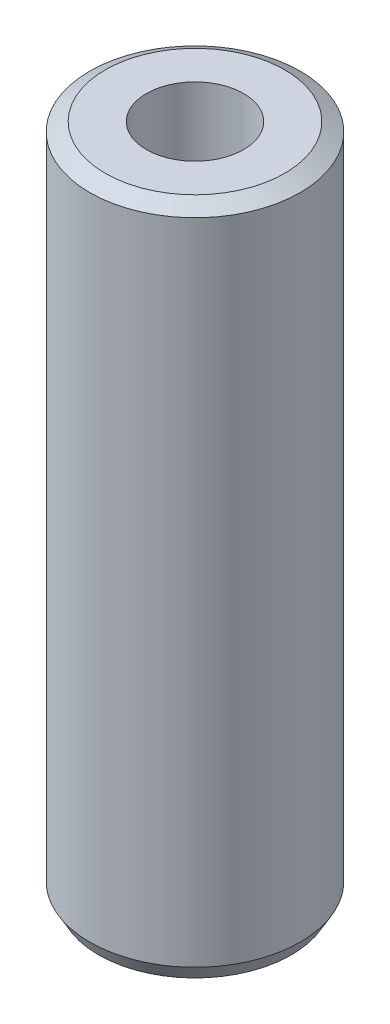
SolidWorks part; units mm, degrees
ref_plane "Front Plane" through (0, 0, 0) normal (0, 0, 1) x (1, 0, 0)
ref_plane "Top Plane" through (0, 0, 0) normal (0, 1, 0) x (1, 0, 0)
ref_plane "Right Plane" through (0, 0, 0) normal (1, 0, 0) x (0, 0, -1)
sketch "Sketch1" plane through (0, 0, 0) normal (0, 1, 0) x (1, 0, 0)
  circle A0 centre (0, 0) radius 55
  dimension "SHAFT_OD" = 110
extrude "Boss-Extrude1" add sketch "Sketch1" along normal blind 351.9378
sketch "Sketch2" plane through (0, 0, 0) normal (0, 1, 0) x (1, 0, 0)
  circle A0 centre (0, 0) radius 25.4016
  dimension "BORE_D" = 50.8031
extrude "Cut-Extrude1" cut sketch "Sketch2" along normal through all
chamfer "Chamfer1" distance 4.6398 angle 60.271 2 edges at (0, 351.9378, 55) (0, 0, 55) first distance on face at (0, 351.9378, 55) first distance on face at (0, 0, 25.4016)
